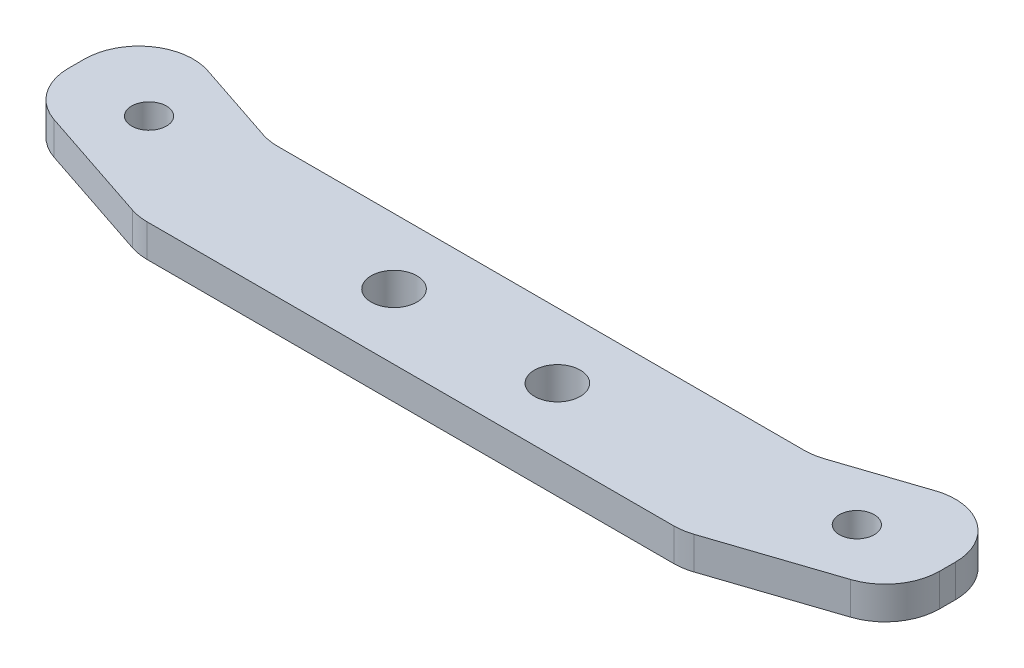
SolidWorks part; units mm, degrees
material "Carbon Fiber"
ref_plane "Front Plane" through (0, 0, 0) normal (0, 0, 1) x (1, 0, 0)
ref_plane "Top Plane" through (0, 0, 0) normal (0, 1, 0) x (1, 0, 0)
ref_plane "Right Plane" through (0, 0, 0) normal (1, 0, 0) x (0, 0, -1)
sketch "Sketch1" plane through (0, 0, 0) normal (0, 1, 0) x (1, 0, 0)
  line L0 (0, 6) -> (15, 1) construction
  line L2 (0, 0) -> (0, 12)
  line L4 (80, 0) -> (80, 12)
  line L5 (40, 7) -> (40, -5) construction
  line L6 (0, 12) -> (15, 7)
  line L7 (15, 7) -> (65, 7)
  line L8 (65, 7) -> (80, 12)
  line L9 (0, 0) -> (15, -5)
  line L10 (15, -5) -> (65, -5)
  line L11 (65, -5) -> (80, 0)
  line L12 (15, 1) -> (65, 1) construction
  line L13 (65, 1) -> (80, 6) construction
  line L14 (15, 7) -> (15, 1) construction
  line L15 (15, 1) -> (15, -5) construction
  line L16 (65, 7) -> (65, 1) construction
  line L17 (65, 1) -> (65, -5) construction
  circle A0 centre (7.5, 3.5) radius 1.6
  circle A2 centre (32.5, 1) radius 2.1
  circle A3 centre (72.5, 3.5) radius 1.6
  circle A4 centre (47.5, 1) radius 2.1
  dimension "D3" = 7.5
  dimension "D4" = 7.5
  dimension "D5" = 4.2
  dimension "D6" = 3.2
  dimension "D1" = 80
  dimension "D2" = 12
  dimension "D7" = 5
  dimension "D8" = 15
extrude "Boss-Extrude1" add sketch "Sketch1" along normal blind 3
fillet "Fillet1" radius 5 8 edges at (0, 1.5, 0) (15, 1.5, -7) (65, 1.5, -7) (80, 1.5, -12) (80, 1.5, 0) (65, 1.5, 5) (15, 1.5, 5) (0, 1.5, -12)
